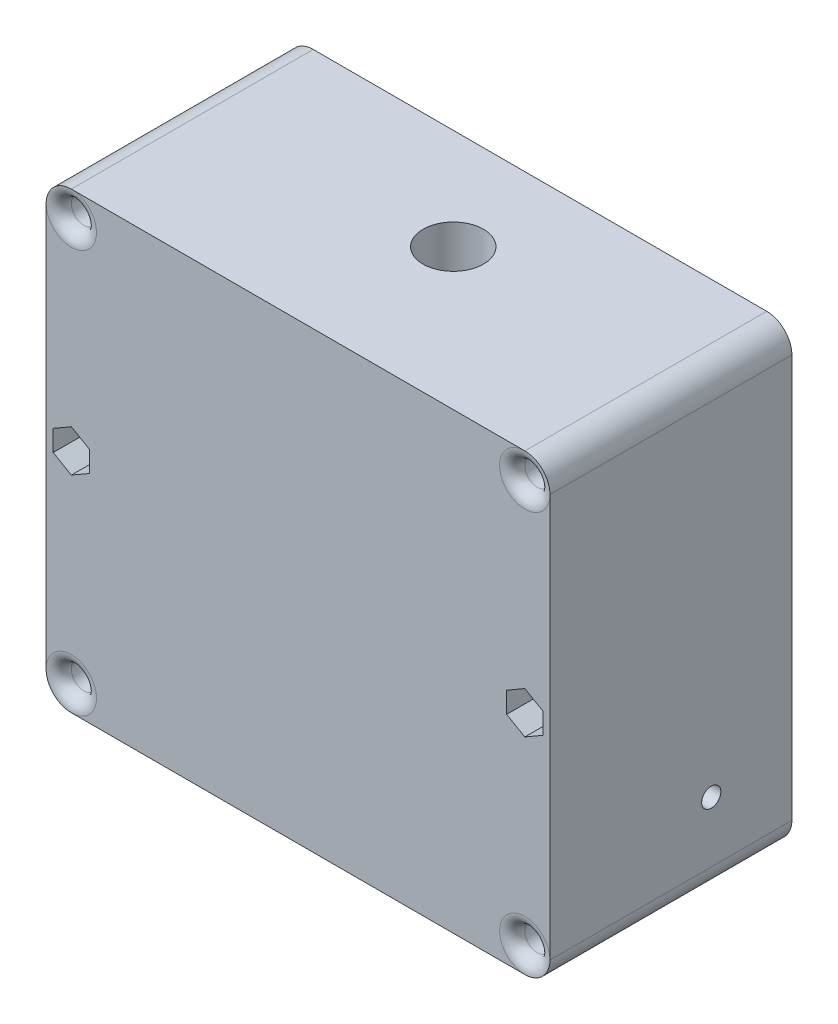
SolidWorks part; units mm, degrees
ref_plane "Front Plane" through (0, 0, 0) normal (0, 0, 1) x (1, 0, 0)
ref_plane "Top Plane" through (0, 0, 0) normal (0, 1, 0) x (1, 0, 0)
ref_plane "Right Plane" through (0, 0, 0) normal (1, 0, 0) x (0, 0, -1)
sketch "Sketch2" plane through (0, 0, 0) normal (0, 0, 1) x (1, 0, 0)
  line L0 (6.35, 57.15) -> (6.35, 114.3) construction
  line L1 (0, 0) -> (127, 0)
  line L2 (0, 0) -> (0, 114.3)
  line L3 (0, 114.3) -> (127, 114.3)
  line L4 (127, 0) -> (127, 114.3)
  line L5 (12.7, 12.7) -> (114.3, 12.7)
  line L6 (12.7, 12.7) -> (12.7, 101.6)
  line L7 (12.7, 101.6) -> (114.3, 101.6)
  line L8 (114.3, 12.7) -> (114.3, 101.6)
  line L9 (6.35, 57.15) -> (6.35, 0) construction
  line L10 (6.35, 57.15) -> (0, 57.15) construction
  line L11 (6.35, 57.15) -> (12.7, 57.15) construction
  line L12 (120.65, 57.15) -> (120.65, 107.95) construction
  line L13 (120.65, 57.15) -> (120.65, 6.35) construction
  line L14 (120.65, 57.15) -> (114.3, 57.15) construction
  line L15 (120.65, 57.15) -> (127, 57.15) construction
  circle A0 centre (6.35, 107.95) radius 3.175
  circle A1 centre (120.65, 107.95) radius 3.175
  circle A2 centre (120.65, 6.35) radius 3.175
  circle A3 centre (6.35, 6.35) radius 3.175
  circle A4 centre (6.35, 57.15) radius 2.54
  circle A5 centre (120.65, 57.15) radius 2.54
  dimension "D7" = 6.35
  dimension "D8" = 6.35
  dimension "D9" = 6.35
  dimension "D10" = 6.35
  dimension "D19" = 5.08
  dimension "D20" = 5.08
  dimension "D1" = 101.6
  dimension "D2" = 88.9
  dimension "D3" = 12.7
  dimension "D4" = 12.7
  dimension "D5" = 12.7
  dimension "D6" = 12.7
  dimension "D11" = 6.35
  dimension "D12" = 6.35
  dimension "D13" = 6.35
  dimension "D14" = 6.35
  dimension "D15" = 6.35
  dimension "D16" = 6.35
  dimension "D17" = 6.35
  dimension "D18" = 6.35
extrude "Boss-Extrude2" add sketch "Sketch2" along normal blind 3.81 contours L2 L1 L4 L3 | A4 | A5 | A1 | A0 | A3 | A2
fillet "Fillet1" radius 3.175 4 edges at (9.525, 6.35, 3.81) (123.825, 107.95, 3.81) (9.525, 107.95, 3.81) (123.825, 6.35, 3.81)
extrude "Boss-Extrude3" add sketch "Sketch2<4>" against normal blind 57.15
sketch "Sketch2<4>" plane through (0, 0, 0) normal (0, 0, 1) x (1, 0, 0) same geometry as "Sketch2"
fillet "Fillet3" radius 6.35 4 edges at (0, 0, -26.67) (127, 0, -26.67) (127, 114.3, -26.67) (0, 114.3, -26.67)
sketch "Sketch3" plane through (0, 0, 0) normal (0, 0, -1) x (-1, 0, 0)
  line L0 (-101.6, 38.1) -> (-114.3, 38.1)
  line L1 (-98.425, 12.7) -> (-46.863, 12.7)
  line L2 (-98.425, 12.7) -> (-98.425, 94.742)
  line L3 (-98.425, 94.742) -> (-46.863, 94.742)
  line L4 (-46.863, 12.7) -> (-46.863, 94.742)
  line L5 (-101.6, 101.6) -> (-43.688, 101.6)
  line L6 (-101.6, 101.6) -> (-101.6, 38.1)
  line L7 (-101.6, 12.7) -> (-43.688, 12.7)
  line L8 (-43.688, 101.6) -> (-43.688, 12.7)
  line L9 (-114.3, 101.6) -> (-12.7, 101.6) construction
  line L10 (-12.7, 12.7) -> (-114.3, 12.7) construction
  line L11 (-43.688, 12.7) -> (-46.863, 12.7)
  line L12 (-98.425, 12.7) -> (-101.6, 12.7)
  line L13 (-46.863, 44.45) -> (-43.688, 44.45)
  line L14 (-43.688, 69.85) -> (-46.863, 69.85)
  line L15 (-114.3, 12.7) -> (-114.3, 101.6) construction
  line L16 (-114.3, 38.1) -> (-114.3, 34.925)
  line L17 (-114.3, 34.925) -> (-101.6, 34.925)
  line L18 (-101.6, 34.925) -> (-101.6, 12.7)
  line M11 (-12.7, 101.6) -> (-114.3, 101.6)
  line M12 (-114.3, 101.6) -> (-114.3, 12.7)
  line M13 (-114.3, 12.7) -> (-12.7, 12.7)
  dimension "D1" = 82.042
  dimension "D2" = 51.562
  dimension "D3" = 3.175
  dimension "D4" = 3.175
  dimension "D5" = 25.4
  dimension "D6" = 31.75
  dimension "D7" = 12.7
  dimension "D8" = 63.5
  dimension "D9" = 3.175
extrude "Boss-Extrude4" add sketch "Sketch3" along normal blind 7.62 contours L17 L18 L2 L3 L4 L14 L8 L6 L0 M13 M11 M12 | L13 L4 L8 M13 region at (100.4647, 69.85, 0) region at (45.2755, 28.575, 0)
sketch "Sketch4" plane through (0, 0, -7.62) normal (0, 0, -1) x (-1, 0, 0)
  line L1 (-114.3, 34.925) -> (-101.6, 34.925)
  line L2 (-114.3, 34.925) -> (-114.3, 38.1)
  line L3 (-114.3, 38.1) -> (-101.6, 38.1)
  line L4 (-101.6, 34.925) -> (-101.6, 38.1)
extrude "Boss-Extrude5" add sketch "Sketch4" along normal blind 10.16
sketch "Sketch5" plane through (0, 0, -7.62) normal (0, 0, -1) x (-1, 0, 0)
  line L0 (-43.688, 101.6) -> (-101.6, 101.6) construction
  line L1 (-101.6, 34.925) -> (-98.425, 34.925)
  line L2 (-101.6, 34.925) -> (-101.6, 101.6)
  line L3 (-101.6, 101.6) -> (-98.425, 101.6)
  line L4 (-98.425, 34.925) -> (-98.425, 101.6)
  line L5 (-98.425, 12.7) -> (-98.425, 94.742) construction
extrude "Boss-Extrude6" add sketch "Sketch5" along normal blind 45.72
sketch "Sketch6" plane through (0, 0, 3.81) normal (0, 0, 1) x (1, 0, 0)
  line L0 (0, 6.35) -> (0, 107.95) construction
  line L1 (6.35, 0) -> (120.65, 0) construction
  line L2 (1.778, 54.5104) -> (1.778, 59.7896)
  line L3 (1.778, 59.7896) -> (6.35, 62.4293)
  line L4 (6.35, 62.4293) -> (10.922, 59.7896)
  line L5 (10.922, 59.7896) -> (10.922, 54.5104)
  line L6 (10.922, 54.5104) -> (6.35, 51.8707)
  line L7 (6.35, 51.8707) -> (1.778, 54.5104)
  line L8 (125.222, 54.5104) -> (125.222, 59.7896)
  line L9 (125.222, 59.7896) -> (120.65, 62.4293)
  line L10 (120.65, 62.4293) -> (116.078, 59.7896)
  line L11 (116.078, 59.7896) -> (116.078, 54.5104)
  line L12 (116.078, 54.5104) -> (120.65, 51.8707)
  line L13 (120.65, 51.8707) -> (125.222, 54.5104)
  circle A0 centre (6.35, 57.15) radius 2.54
  circle A1 centre (6.35, 57.15) radius 4.572
  circle A2 centre (120.65, 57.15) radius 2.54
  circle A3 centre (120.65, 57.15) radius 4.572
  circle M16 centre (120.65, 57.15) radius 2.54
  circle M17 centre (6.35, 57.15) radius 2.54
  dimension "D1" = 9.144
  dimension "D2" = 9.144
  dimension "D3" = 5.08
  dimension "D4" = 6.35
  dimension "D5" = 120.65
  dimension "D6" = 57.15
  dimension "D7" = 120
  dimension "D8" = 120
  dimension "D9" = 120
  dimension "D10" = 120
  dimension "D11" = 120
  dimension "D12" = 120
  dimension "D13" = 120
  dimension "120" = 120
extrude "Cut-Extrude1" cut sketch "Sketch6" against normal blind 10.16 contours A1 L4 L3 | A1 L3 L2 | A1 L2 L7 | A1 L7 L6 | A1 L6 L5 | A1 L5 L4 | A1 M17 | M17 | A3 L10 L11 | A3 L11 L12 | A3 L12 L13 | A3 L13 L8 | A3 L8 L9 | A3 L9 L10 | A3 M16 | M16 region at (2.2576, 54.7873, 3.81) region at (2.2576, 59.5127, 3.81) region at (2.5025, 59.3713, 3.81) region at (6.35, 52.4245, 3.81) region at (6.35, 61.8755, 3.81) region at (10.4424, 54.7873, 3.81) region at (10.4424, 59.5127, 3.81) region at (124.7424, 54.7873, 3.81) region at (124.7424, 59.5127, 3.81) region at (124.4975, 54.9287, 3.81) region at (120.65, 52.4245, 3.81) region at (120.65, 61.8755, 3.81) region at (116.5576, 54.7873, 3.81) region at (116.5576, 59.5127, 3.81) region at (6.35, 57.15, 3.81) region at (120.65, 57.15, 3.81)
sketch "Sketch7" plane through (0, 114.3, 0) normal (0, 1, 0) x (1, 0, 0)
  line L0 (59.436, 31.75) -> (6.35, 31.75) construction
  line L1 (74.676, 31.75) -> (120.65, 31.75) construction
  line L2 (6.35, 57.15) -> (6.35, -3.81) construction
  line L3 (120.65, -3.81) -> (120.65, 57.15) construction
  line L4 (67.056, 24.13) -> (67.056, -3.81) construction
  line L5 (6.35, -3.81) -> (120.65, -3.81) construction
  circle A0 centre (67.056, 31.75) radius 7.62
  dimension "D1" = 45.974
  dimension "D2" = 53.086
  dimension "D3" = 27.94
extrude "Cut-Extrude2" cut sketch "Sketch7" against normal blind 15.24
sketch "Sketch8" plane through (114.3, 0, 0) normal (-1, 0, 0) x (0, 0, 1)
  line L0 (-57.15, 12.7) -> (0, 12.7) construction
  line L1 (-57.15, 12.7) -> (-57.15, 101.6) construction
  circle A0 centre (-36.83, 21.59) radius 2.413
  point P2 (0, 0)
  dimension "D1" = 4.826
  dimension "D2" = 8.89
  dimension "D3" = 20.32
extrude "Cut-Extrude3" cut sketch "Sketch8" against normal blind 15.24
